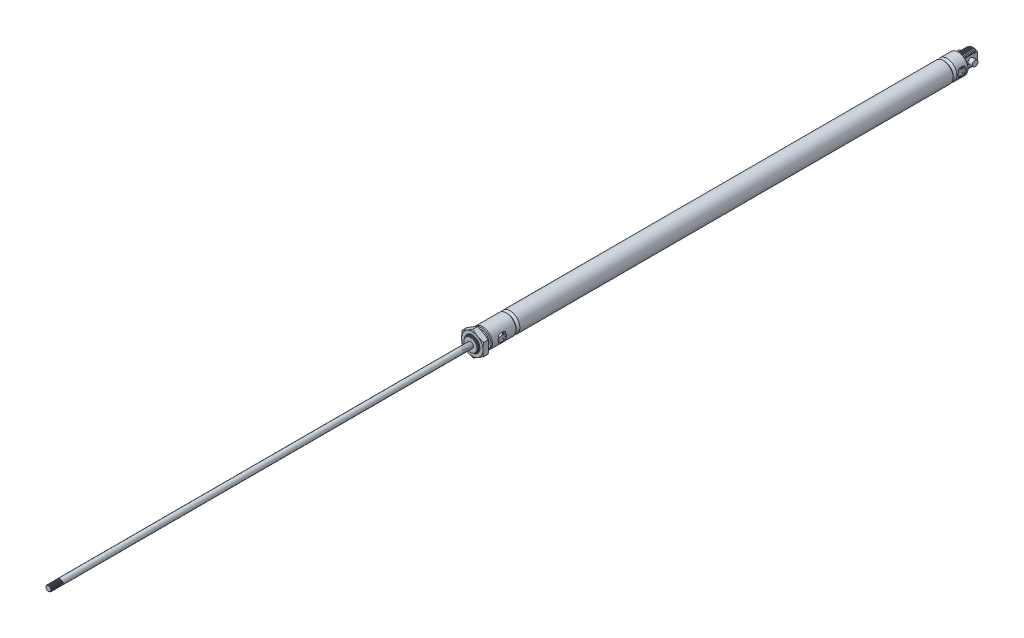
SolidWorks part; units mm, degrees
ref_plane "Front" through (0, 0, 0) normal (0, 0, 1) x (1, 0, 0)
ref_plane "Top" through (0, 0, 0) normal (0, 1, 0) x (1, 0, 0)
ref_plane "Right" through (0, 0, 0) normal (1, 0, 0) x (0, 0, -1)
sketch "Sketch1" plane through (0, 0, 0) normal (1, 0, 0) x (0, 0, -1)
  line L0 (-286.131, 0) -> (286.131, 0) construction
  line L1 (-273.431, -7.9375) -> (-273.431, 0) construction
  line L2 (-273.431, 7.9375) -> (-260.731, 7.9375) construction
  line L3 (-260.731, 0) -> (-260.731, 10.922)
  line L4 (-260.731, 10.922) -> (286.131, 10.922)
  line L5 (270.383, 10.922) -> (270.383, 7.9375) construction
  line L6 (270.383, 7.9375) -> (286.131, 7.9375) construction
  line L7 (286.131, 10.922) -> (286.131, 0)
  line L8 (286.131, 0) -> (301.879, 0) construction
  line L9 (-273.431, -7.9375) -> (-260.731, -7.9375) construction
  line L10 (-260.731, -7.9375) -> (-260.731, -10.922) construction
  line L11 (-260.731, -10.922) -> (286.131, -10.922) construction
  line L12 (270.383, -10.922) -> (270.383, -7.9375) construction
  line L13 (270.383, -7.9375) -> (286.131, -7.9375) construction
  line L14 (-263.017, 9.525) -> (-263.017, 0) construction
  line L18 (-273.431, 3.175) -> (-286.131, 3.175) construction
  line L19 (-286.131, 3.175) -> (-286.131, -3.175) construction
  line L20 (-286.131, -3.175) -> (-273.431, -3.175) construction
  line L24 (-273.431, 4.7625) -> (-263.017, 4.7625) construction
  line L25 (286.131, 0) -> (286.131, -10.922) construction
  line L26 (-273.431, 0) -> (-273.431, 7.9375) construction
  line L28 (-260.731, 0) -> (286.131, 0)
  line L29 (-268.224, 4.7625) -> (-268.224, 7.9375) construction
  line L30 (-260.731, 9.525) -> (-263.017, 9.525) construction
  dimension "D1" = 19.05
  dimension "J Flat" = 15.875
  dimension "E OD" = 21.844
  dimension "K Flat Depth" = 15.748
  dimension "RM Pilot" = 15.875
  dimension "G Pilot Length" = 12.7
  dimension "Shaft Dia" = 6.35
  dimension "A Thread Length" = 12.7
  dimension "Total Length" = 572.262
  dimension "V Pilot Length" = 2.286
revolve "Revolve1" add sketch "Sketch1" angle 360 about L8 reverse direction yes
sketch "Sketch58" plane through (0, 0, 0) normal (1, 0, 0) x (0, 0, -1)
  line L0 (286.131, 0) -> (301.879, 0) construction
  line L1 (270.383, 10.922) -> (286.131, 10.922)
  line L2 (270.383, 10.922) -> (270.383, 7.9375)
  line L3 (270.383, 7.9375) -> (286.131, 7.9375)
  line L4 (286.131, 10.922) -> (286.131, 7.9375)
  line L5 (286.131, 0) -> (301.879, 0) construction
revolve "Cut-Revolve25" cut sketch "Sketch58" angle 360 about L5
sketch "Sketch59" plane through (0, 0, -286.131) normal (0, 0, -1) x (-1, 0, 0)
  line L0 (-4.7625, -7.9375) -> (4.7625, 7.9375) construction
  line L1 (-4.7625, 7.9375) -> (4.7625, 7.9375)
  line L2 (-4.7625, 7.9375) -> (-4.7625, -7.9375)
  line L3 (-4.7625, -7.9375) -> (4.7625, -7.9375)
  line L4 (4.7625, 7.9375) -> (4.7625, -7.9375)
  dimension "D1" = 9.525
extrude "Cut-Extrude3" cut sketch "Sketch59" against normal up to surface (15.748 mm away) flip side to cut up to face at (7.9375, 0, -270.383)
chamfer "Chamfer1" distance 0.7874 angle 45 4 edges at (-10.922, 0, 260.731) (10.922, 0, -270.383) (0, 7.9375, -286.131) (0, -7.9375, -286.131)
sketch "Sketch4" plane through (0, 0, 0) normal (1, 0, 0) x (0, 0, -1)
  line L0 (-273.431, 0) -> (-273.431, 7.9375) construction
  line L1 (-286.131, 0) -> (286.131, 0) construction
  line L2 (-260.731, 0) -> (-260.731, 10.922) construction
  line L3 (-273.431, 7.9375) -> (-260.731, 7.9375) construction
  line L4 (-273.431, 0) -> (-273.431, 7.9375)
  line L5 (-273.431, 0) -> (-260.731, 0)
  line L6 (-260.731, 0) -> (-260.731, 7.9375)
  line L7 (-273.431, 7.9375) -> (-260.731, 7.9375)
  line L8 (-273.431, -7.9375) -> (-260.731, -7.9375) construction
  line L9 (-273.431, -7.9375) -> (-260.731, -7.9375) construction
revolve "Revolve2" add sketch "Sketch4" angle 360 about L5
sketch "Sketch5" plane through (0, 0, 0) normal (1, 0, 0) x (0, 0, -1)
  line L0 (-273.431, 7.9375) -> (-273.431, -7.9375) construction
  line L1 (-273.431, -7.9375) -> (-272.0199, -7.9375) construction
  line L2 (-272.0199, -7.9375) -> (-273.431, 7.9375) construction
  line L3 (-273.431, 7.9375) -> (-273.2553, 7.9531) construction
  line L4 (-273.2553, 7.9531) -> (-272.0254, 8.0624)
  line L5 (-272.0254, 8.0624) -> (-272.397, 7.2626)
  line L6 (-272.397, 7.2626) -> (-272.7484, 7.2314)
  line L7 (-272.7484, 7.2314) -> (-273.2553, 7.9531)
  line L8 (-272.6404, 8.0078) -> (-272.5727, 7.247) construction
  line L9 (-273.431, 7.9375) -> (-272.6341, 7.9375) construction
  line L10 (-272.6341, 7.9375) -> (-271.223, -7.9375) construction
  line L11 (-271.223, -7.9375) -> (-272.0199, -7.9375) construction
  line L12 (-273.431, 0) -> (-273.431, 7.9375) construction
  line L13 (-273.431, 7.9375) -> (-260.731, 7.9375) construction
  line L14 (-273.431, -7.9375) -> (-260.731, -7.9375) construction
  line L15 (-273.431, -0.1335) -> (-270.4261, 0.1335) construction
  point P19 (-271.9286, 0)
  dimension "D1" = 0.1764
  dimension "D2" = 0.3528
  dimension "Thread Pitch" = 1.4111
  dimension "D4" = 60
  dimension "D5" = 1.4111
revolve "Cut-Revolve2" cut sketch "Sketch5" angle 360 about L15
sketch "Sketch6" plane through (0, 0, 0) normal (1, 0, 0) x (0, 0, -1)
  line L0 (-273.431, 7.2314) -> (-272.208, 7.9375)
  line L1 (-272.208, 7.9375) -> (-273.431, 7.9375)
  line L2 (-273.431, 7.9375) -> (-273.431, 7.2314)
  line L3 (0, 0) -> (-273.431, 0) construction
  line L4 (-273.431, 0) -> (-273.431, 7.2314) construction
  line L5 (-273.431, 7.9375) -> (-260.731, 7.9375) construction
  line L6 (-273.431, 0) -> (-273.431, 7.9375) construction
  line L7 (-272.7484, 7.2314) -> (-273.431, 7.2314) construction
  dimension "D1" = 60
revolve "Cut-Revolve3" cut sketch "Sketch6" angle 360 about L3
pattern_linear "LPattern2" count 2 spacing 1.4111 along (0, 0, 1) count 9 spacing 1.4111 along (0, 0, -1) of "Cut-Revolve2"
sketch "Sketch53" plane through (0, 0, 0) normal (1, 0, 0) x (0, 0, -1)
  line L0 (-273.431, 0) -> (-260.731, 0) construction
  line L1 (-260.731, 7.9375) -> (-263.017, 7.9375)
  line L2 (-260.731, 7.9375) -> (-260.731, 0)
  line L3 (-260.731, 0) -> (-263.017, 0)
  line L4 (-263.017, 7.9375) -> (-263.017, 0)
  line L5 (-263.017, 9.525) -> (-263.017, 0) construction
  line L6 (-273.431, 7.9375) -> (-260.731, 7.9375) construction
  line L7 (-260.731, 0) -> (-260.731, 10.922) construction
revolve "Revolve4" add sketch "Sketch53" angle 360 about L3
sketch "Sketch62" plane through (0, 0, 0) normal (1, 0, 0) x (0, 0, -1)
  line L0 (270.383, 7.9375) -> (270.383, -7.9375) construction
  line L1 (270.383, -7.9375) -> (271.7941, -7.9375) construction
  line L2 (271.7941, -7.9375) -> (270.383, 7.9375) construction
  line L3 (270.383, 7.9375) -> (270.5587, 7.9531) construction
  line L4 (270.5587, 7.9531) -> (271.7886, 8.0624)
  line L5 (271.7886, 8.0624) -> (271.417, 7.2626)
  line L6 (271.417, 7.2626) -> (271.0656, 7.2314)
  line L7 (271.0656, 7.2314) -> (270.5587, 7.9531)
  line L8 (271.2413, 7.247) -> (271.1736, 8.0078) construction
  line L9 (270.383, 7.9375) -> (271.1799, 7.9375) construction
  line L10 (271.1799, 7.9375) -> (272.591, -7.9375) construction
  line L11 (272.591, -7.9375) -> (271.7941, -7.9375) construction
  line L12 (270.383, -0.1335) -> (273.3879, 0.1335) construction
  line L13 (270.383, 7.9375) -> (286.131, 7.9375) construction
  line L14 (270.383, 10.922) -> (270.383, 7.9375) construction
  line L15 (270.383, -7.9375) -> (286.131, -7.9375) construction
  point P13 (271.8854, 0)
  dimension "D1" = 60
  dimension "D2" = 0.3528
  dimension "D3" = 0.1764
  dimension "D4" = 1.4111
  dimension "D5" = 1.4111
revolve "Cut-Revolve26" cut sketch "Sketch62" angle 360 about L12
pattern_linear "LPattern5" count 11 spacing 1.4111 along (0, 0, -1) of "Cut-Revolve26"
sketch "Sketch60" plane through (0, 0, 0) normal (1, 0, 0) x (0, 0, -1)
  line L0 (-260.731, 0) -> (286.131, 0) construction
  line L1 (286.131, 10.922) -> (286.131, 0) construction
  circle A0 centre (279.019, 0) radius 3.175
  dimension "D2" = 6.35
  dimension "D1" = 7.112
extrude "Extrude2" add sketch "Sketch60" along normal mid plane 19.05
sketch "Sketch7" plane through (0, 0, 0) normal (1, 0, 0) x (0, 0, -1)
  line L0 (-273.431, 3.2004) -> (-257.556, 3.2004)
  line L1 (-257.556, 3.2004) -> (-257.556, 6.3627)
  line L2 (-257.556, 9.525) -> (-215.392, 9.525) construction
  line L3 (-209.042, 9.525) -> (248.158, 9.525)
  line L4 (248.158, 0) -> (-273.431, 0)
  line L5 (-273.431, 0) -> (-273.431, 3.2004)
  line L6 (-273.431, 0) -> (-273.431, 7.9375) construction
  line L7 (-260.731, 0) -> (286.131, 0) construction
  line L8 (248.158, 0) -> (301.879, 0) construction
  line L9 (-260.731, 0) -> (-260.731, 10.922) construction
  line L10 (248.158, 9.525) -> (248.158, 0)
  line L11 (253.111, 10.922) -> (254.508, 9.525)
  line L12 (-257.556, 6.3627) -> (-215.392, 6.3627)
  line L13 (-215.392, 6.3627) -> (-215.392, 9.525)
  line L14 (-257.556, 6.3627) -> (-257.556, 9.525) construction
  line L15 (-215.392, 9.525) -> (-209.042, 9.525)
  line L17 (254.508, 9.525) -> (254.508, 8.128)
  line L18 (254.508, 8.128) -> (257.302, 10.922)
  line L19 (257.302, 10.922) -> (253.111, 10.922)
  line L20 (254.508, 9.525) -> (254.508, 10.922) construction
  line L21 (-260.731, 10.922) -> (286.131, 10.922) construction
  line L22 (270.383, 10.922) -> (270.383, 7.9375) construction
  line L23 (-233.553, 10.922) -> (-232.156, 9.525)
  line L24 (-232.156, 9.525) -> (-232.156, 8.128)
  line L25 (-232.156, 8.128) -> (-229.362, 10.922)
  line L26 (-229.362, 10.922) -> (-233.553, 10.922)
  line L27 (-232.156, 9.525) -> (-232.156, 10.922) construction
  line L28 (-273.431, 3.175) -> (-286.131, 3.175) construction
  dimension "D1" = 0.0254
  dimension "Bore Dia" = 19.05
  dimension "D2" = 6.35
  dimension "D3" = 45
  dimension "Stroke" = 457.2
  dimension "D4" = 3.175
  dimension "D5" = 6.35
  dimension "D6" = 15.875
  dimension "D7" = 28.575
revolve "Cut-Revolve5" cut sketch "Sketch7" angle 360 about L8
sketch "Sketch8" plane through (0, 0, 0) normal (1, 0, 0) x (0, 0, -1)
  line L2 (241.808, 9.4742) -> (248.158, 9.4742)
  line L3 (248.158, 9.4742) -> (248.158, 0)
  line L4 (-286.131, 3.175) -> (-286.131, -3.175) construction
  line L6 (-286.131, 3.175) -> (-286.131, 0)
  line L7 (248.158, 0) -> (-286.131, 0)
  line L8 (-286.131, 0) -> (286.131, 0) construction
  line L9 (-209.042, 9.525) -> (248.158, 9.525) construction
  line L11 (248.158, 9.525) -> (248.158, 0) construction
  line L15 (241.808, 3.175) -> (241.808, 9.4742)
  line L16 (241.808, 3.175) -> (-286.131, 3.175)
  dimension "D1" = 0.0508
  dimension "D2" = 6.35
revolve "Revolve3" add sketch "Sketch8" angle 360 about L7
sketch "Sketch10" plane through (0, 0, 0) normal (1, 0, 0) x (0, 0, -1)
  line L0 (-286.131, 3.175) -> (-286.131, -3.175) construction
  line L1 (-286.131, -3.175) -> (-285.2239, -3.175) construction
  line L2 (-285.2239, -3.175) -> (-286.131, 3.175) construction
  line L3 (-286.131, 3.175) -> (-286.0187, 3.191) construction
  line L4 (-286.0187, 3.191) -> (-285.233, 3.3033)
  line L5 (-285.233, 3.3033) -> (-285.4442, 2.7771)
  line L6 (-285.4442, 2.7771) -> (-285.6687, 2.7451)
  line L7 (-285.6687, 2.7451) -> (-286.0187, 3.191)
  line L8 (-285.6259, 3.2472) -> (-285.5564, 2.7611) construction
  line L9 (-286.131, 3.175) -> (-285.6156, 3.175) construction
  line L10 (-285.6156, 3.175) -> (-284.7084, -3.175) construction
  line L11 (-284.7084, -3.175) -> (-285.2239, -3.175) construction
  line L12 (-286.131, 3.175) -> (-286.131, -3.175) construction
  line L13 (-273.431, 3.175) -> (-286.131, 3.175) construction
  line L14 (-286.131, -3.175) -> (-273.431, -3.175) construction
  line L15 (-286.131, -0.1384) -> (-284.193, 0.1384) construction
  point P19 (-285.162, 0)
  dimension "D1" = 0.1134
  dimension "D2" = 0.2268
  dimension "Shaft Thread Pitch" = 0.9071
  dimension "D4" = 0.9071
  dimension "D5" = 60
revolve "Cut-Revolve6" cut sketch "Sketch10" angle 360 about L15
sketch "Sketch11" plane through (0, 0, 0) normal (1, 0, 0) x (0, 0, -1)
  line L0 (-286.131, 3.175) -> (-285.3863, 3.175)
  line L1 (-285.3863, 3.175) -> (-286.131, 2.7451)
  line L2 (-286.131, 2.7451) -> (-286.131, 3.175)
  line L3 (0, 0) -> (-286.131, 0) construction
  line L4 (-286.131, 0) -> (-286.131, 2.7451) construction
  line L5 (-273.431, 3.175) -> (-286.131, 3.175) construction
  line L6 (-286.131, 3.175) -> (-286.131, -3.175) construction
  line L7 (-285.6687, 2.7451) -> (-286.131, 2.7451) construction
  dimension "D1" = 30
revolve "Cut-Revolve7" cut sketch "Sketch11" angle 360 about L3
pattern_linear "LPattern3" count 2 spacing 0.9071 along (0, 0, 1) count 14 spacing 0.9071 along (0, 0, -1) of "Cut-Revolve6"
pattern_linear "LPattern4" count 2 spacing 457.2 along (0, 0, 1) of bodies 122
ref_plane "Plane4" through (0, 0, -263.271) normal (0, 0, -1) x (-1, 0, 0)
ref_axis "Axis3" through (0, -15.123, -263.271) along (0, 1, 0)
ref_plane "Plane6" through (0, 0, -263.271) normal (0, 0, 1) x (1, 0, 0)
sketch "Sketch13" plane through (-356.4319, -1.7517, -263.271) normal (0, 0, 1) x (1, 0, 0)
  line L0 (355.9239, 1.7517) -> (355.9239, 5.9543)
  line L1 (355.9239, 5.9543) -> (356.3686, 6.7833) construction
  line L2 (356.3686, 6.7833) -> (356.8642, 5.9837) construction
  line L3 (356.8642, 5.9837) -> (357.3089, 6.8127) construction
  line L4 (357.3089, 6.8127) -> (357.8045, 6.013) construction
  line L5 (356.8811, 6.0153) -> (357.2919, 6.781)
  line L6 (357.2919, 6.781) -> (357.3278, 6.7822)
  line L7 (357.3278, 6.7822) -> (357.7856, 6.0435)
  line L8 (357.7856, 6.0435) -> (357.8214, 6.0446)
  line L9 (355.9239, 5.9543) -> (357.8045, 6.013) construction
  line L10 (356.3686, 6.7833) -> (357.3089, 6.8127) construction
  line L11 (356.1462, 6.3688) -> (357.5567, 6.4128) construction
  line L12 (355.9239, 1.7517) -> (351.7213, 1.7517) construction
  line L13 (357.8214, 6.0446) -> (358.2322, 6.8104)
  line L14 (355.9409, 5.9859) -> (356.3516, 6.7517)
  line L15 (356.3516, 6.7517) -> (356.3875, 6.7528)
  line L16 (356.3875, 6.7528) -> (356.8453, 6.0141)
  line L17 (356.8453, 6.0141) -> (356.8811, 6.0153)
  line L18 (356.1462, 6.3688) -> (355.9239, 6.3618) construction
  line L19 (355.9239, 6.3618) -> (355.9239, 5.9543) construction
  line L20 (356.1462, -2.8653) -> (355.9239, -2.8584) construction
  line L21 (355.9409, 5.9859) -> (355.9239, 5.9543)
  line L22 (358.2322, 6.8104) -> (358.268, 6.8116)
  line L23 (358.268, 6.8116) -> (358.7258, 6.0729)
  line L24 (358.7258, 6.0729) -> (358.7617, 6.074)
  line L25 (358.7617, 6.074) -> (359.1725, 6.8398)
  line L26 (359.1725, 6.8398) -> (359.2083, 6.8409)
  line L27 (359.2083, 6.8409) -> (359.6661, 6.1023)
  line L28 (359.6661, 6.1023) -> (359.702, 6.1034)
  line L29 (359.702, 6.1034) -> (360.1128, 6.8692)
  line L30 (360.1128, 6.8692) -> (360.1486, 6.8703)
  line L31 (360.1486, 6.8703) -> (360.6064, 6.1317)
  line L32 (360.6064, 6.1317) -> (360.6423, 6.1328)
  line L33 (360.6423, 6.1328) -> (361.053, 6.8986)
  line L34 (361.053, 6.8986) -> (361.0889, 6.8997)
  line L35 (361.0889, 6.8997) -> (361.5467, 6.1611)
  line L36 (361.5467, 6.1611) -> (361.5825, 6.1622)
  line L37 (361.5825, 6.1622) -> (361.9933, 6.928)
  line L38 (361.9933, 6.928) -> (362.0292, 6.9291)
  line L39 (362.0292, 6.9291) -> (362.487, 6.1904)
  line L40 (362.487, 6.1904) -> (362.5228, 6.1916)
  line L41 (362.5228, 6.1916) -> (362.9336, 6.9574)
  line L42 (362.9336, 6.9574) -> (362.9695, 6.9585)
  line L43 (362.9695, 6.9585) -> (363.4273, 6.2198)
  line L44 (363.4273, 6.2198) -> (363.4631, 6.221)
  line L45 (363.4631, 6.221) -> (363.8739, 6.9867)
  line L46 (363.8739, 6.9867) -> (363.9097, 6.9879)
  line L47 (363.9097, 6.9879) -> (364.3675, 6.2492)
  line L48 (364.3675, 6.2492) -> (364.4034, 6.2503)
  line L49 (364.4034, 6.2503) -> (364.8142, 7.0161)
  line L50 (364.8142, 7.0161) -> (364.85, 7.0173)
  line L51 (364.85, 7.0173) -> (365.3078, 6.2786)
  line L52 (365.3078, 6.2786) -> (365.3437, 6.2797)
  line L53 (365.3437, 6.2797) -> (365.7545, 7.0455)
  line L54 (365.7545, 7.0455) -> (365.7903, 7.0466)
  line L55 (365.7903, 7.0466) -> (366.2481, 6.308)
  line L56 (366.2481, 6.308) -> (366.284, 6.3091)
  line L57 (366.284, 6.3091) -> (366.6947, 7.0749)
  line L58 (366.6947, 7.0749) -> (366.7306, 7.076)
  line L59 (366.7306, 7.076) -> (367.1884, 6.3374)
  line L60 (367.1884, 6.3374) -> (367.2242, 6.3385)
  line L61 (367.2242, 6.3385) -> (367.635, 7.1043)
  line L62 (367.635, 7.1043) -> (367.6709, 7.1054)
  line L63 (367.6709, 7.1054) -> (368.1287, 6.3668)
  line L64 (368.1287, 6.3668) -> (368.1645, 6.3679)
  line L65 (368.1645, 6.3679) -> (368.5753, 7.1337)
  line L66 (368.5753, 7.1337) -> (368.6111, 7.1348)
  line L67 (368.6111, 7.1348) -> (369.0689, 6.3961)
  line L68 (369.0689, 6.3961) -> (369.1048, 6.3973)
  line L69 (369.1048, 6.3973) -> (369.5156, 7.1631)
  line L70 (369.5156, 7.1631) -> (369.5514, 7.1642)
  line L71 (369.5514, 7.1642) -> (370.0092, 6.4255)
  line L72 (370.0092, 6.4255) -> (370.0451, 6.4267)
  line L73 (355.9239, 1.7517) -> (370.0451, 1.7517)
  line L74 (370.0451, 1.7517) -> (370.0451, 6.4267)
  line L75 (356.3696, 6.7522) -> (356.3686, 6.7833) construction
  line L80 (356.4319, 1.7517) -> (367.3539, 1.7517) construction
  circle A0 centre (356.4319, 1.7517) radius 10.922 construction
  circle A1 centre (356.4319, 1.7517) radius 10.922 construction
  dimension "D1" = 60
  dimension "D2" = 0.031
  dimension "E0" = 9.2202
  dimension "D3" = 0.0359
  dimension "Thread Pitch" = 0.9407
  dimension "Thread Taper" = 3.58
  dimension "L4 Thread Length" = 11.43
revolve "Cut-Revolve22" cut sketch "Sketch13" angle 360 about L12
ref_plane "Plane7" through (0, 0, 248.793) normal (0, 0, 1) x (1, 0, 0)
sketch "Sketch64" plane through (-356.4319, -1.7517, 248.793) normal (0, 0, 1) x (1, 0, 0)
  line L0 (355.9239, 1.7517) -> (355.9239, 5.9543)
  line L1 (355.9239, 5.9543) -> (356.3686, 6.7833) construction
  line L2 (356.3686, 6.7833) -> (356.8642, 5.9837) construction
  line L3 (356.8642, 5.9837) -> (357.3089, 6.8127) construction
  line L4 (357.3089, 6.8127) -> (357.8045, 6.013) construction
  line L5 (356.8896, 6.0311) -> (357.2834, 6.7652)
  line L6 (357.2834, 6.7652) -> (357.3372, 6.7669)
  line L7 (357.3372, 6.7669) -> (357.7761, 6.0588)
  line L8 (357.7761, 6.0588) -> (357.8299, 6.0604)
  line L9 (355.9239, 5.9543) -> (357.8045, 6.013) construction
  line L10 (356.3686, 6.7833) -> (357.3089, 6.8127) construction
  line L11 (356.1462, 6.3688) -> (357.5567, 6.4128) construction
  line L12 (355.9239, 1.7517) -> (351.7213, 1.7517) construction
  line L13 (357.8299, 6.0604) -> (358.2237, 6.7946)
  line L14 (355.9493, 6.0017) -> (356.3432, 6.7359)
  line L15 (356.3432, 6.7359) -> (356.3969, 6.7375)
  line L16 (356.3969, 6.7375) -> (356.8358, 6.0294)
  line L17 (356.8358, 6.0294) -> (356.8896, 6.0311)
  line L18 (356.1462, 6.3688) -> (355.9239, 6.3618) construction
  line L19 (355.9239, 6.3618) -> (355.9239, 5.9543) construction
  line L20 (356.1462, -2.8653) -> (355.9239, -2.8584) construction
  line L21 (355.9493, 6.0017) -> (355.9239, 5.9543)
  line L22 (358.2237, 6.7946) -> (358.2775, 6.7963)
  line L23 (358.2775, 6.7963) -> (358.7164, 6.0882)
  line L24 (358.7164, 6.0882) -> (358.7702, 6.0898)
  line L25 (358.7702, 6.0898) -> (359.164, 6.824)
  line L26 (359.164, 6.824) -> (359.2178, 6.8257)
  line L27 (359.2178, 6.8257) -> (359.6567, 6.1175)
  line L28 (359.6567, 6.1175) -> (359.7105, 6.1192)
  line L29 (359.7105, 6.1192) -> (360.1043, 6.8534)
  line L30 (360.1043, 6.8534) -> (360.1581, 6.8551)
  line L31 (360.1581, 6.8551) -> (360.597, 6.1469)
  line L32 (360.597, 6.1469) -> (360.6507, 6.1486)
  line L33 (360.6507, 6.1486) -> (361.0446, 6.8828)
  line L34 (361.0446, 6.8828) -> (361.0983, 6.8845)
  line L35 (361.0983, 6.8845) -> (361.5372, 6.1763)
  line L36 (361.5372, 6.1763) -> (361.591, 6.178)
  line L37 (361.591, 6.178) -> (361.9849, 6.9122)
  line L38 (361.9849, 6.9122) -> (362.0386, 6.9139)
  line L39 (362.0386, 6.9139) -> (362.4775, 6.2057)
  line L40 (362.4775, 6.2057) -> (362.5313, 6.2074)
  line L41 (362.5313, 6.2074) -> (362.9251, 6.9416)
  line L42 (362.9251, 6.9416) -> (362.9789, 6.9432)
  line L43 (362.9789, 6.9432) -> (363.4178, 6.2351)
  line L44 (363.4178, 6.2351) -> (363.4716, 6.2368)
  line L45 (363.4716, 6.2368) -> (363.8654, 6.9709)
  line L46 (363.8654, 6.9709) -> (363.9192, 6.9726)
  line L47 (363.9192, 6.9726) -> (364.3581, 6.2645)
  line L48 (364.3581, 6.2645) -> (364.4119, 6.2661)
  line L49 (364.4119, 6.2661) -> (364.8057, 7.0003)
  line L50 (364.8057, 7.0003) -> (364.8595, 7.002)
  line L51 (364.8595, 7.002) -> (365.2984, 6.2938)
  line L52 (365.2984, 6.2938) -> (365.3521, 6.2955)
  line L53 (365.3521, 6.2955) -> (365.746, 7.0297)
  line L54 (365.746, 7.0297) -> (365.7997, 7.0314)
  line L55 (365.7997, 7.0314) -> (366.2387, 6.3232)
  line L56 (366.2387, 6.3232) -> (366.2924, 6.3249)
  line L57 (366.2924, 6.3249) -> (366.6863, 7.0591)
  line L58 (366.6863, 7.0591) -> (366.74, 7.0608)
  line L59 (366.74, 7.0608) -> (367.1789, 6.3526)
  line L60 (367.1789, 6.3526) -> (367.2327, 6.3543)
  line L61 (367.2327, 6.3543) -> (367.6265, 7.0885)
  line L62 (367.6265, 7.0885) -> (367.6803, 7.0902)
  line L63 (367.6803, 7.0902) -> (368.1192, 6.382)
  line L64 (368.1192, 6.382) -> (368.173, 6.3837)
  line L65 (368.173, 6.3837) -> (368.5668, 7.1179)
  line L66 (368.5668, 7.1179) -> (368.6206, 7.1196)
  line L67 (368.6206, 7.1196) -> (369.0595, 6.4114)
  line L68 (369.0595, 6.4114) -> (369.1133, 6.4131)
  line L69 (369.1133, 6.4131) -> (369.5071, 7.1473)
  line L70 (369.5071, 7.1473) -> (369.5609, 7.1489)
  line L71 (369.5609, 7.1489) -> (369.9998, 6.4408)
  line L72 (369.9998, 6.4408) -> (370.0536, 6.4425)
  line L73 (355.9239, 1.7517) -> (370.0536, 1.7517)
  line L74 (370.0536, 1.7517) -> (370.0536, 6.4425)
  line L75 (356.37, 6.7367) -> (356.3686, 6.7833) construction
  line L80 (356.4319, 1.7517) -> (367.3539, 1.7517) construction
  circle A1 centre (356.4319, 1.7517) radius 10.922 construction
  circle A2 centre (356.4319, 1.7517) radius 10.922 construction
  dimension "D1" = 60
  dimension "D2" = 0.0466
  dimension "D3" = 0.0538
  dimension "Thread Pitch" = 0.9407
  dimension "D4" = 9.2202
  dimension "Thread Taper" = 3.58
  dimension "L4 Thread Length" = 11.43
revolve "Cut-Revolve27" cut sketch "Sketch64" angle 360 about L73
ref_plane "Plane2" through (0, 0, 268.224) normal (0, 0, 1) x (1, 0, 0)
sketch "Sketch54" plane through (0, 0, 268.224) normal (0, 0, 1) x (1, 0, 0)
  line L1 (0, 13.7482) -> (-11.9062, 6.8741)
  line L2 (-11.9062, 6.8741) -> (-11.9062, -6.8741)
  line L3 (-11.9062, -6.8741) -> (0, -13.7482)
  line L4 (0, -13.7482) -> (11.9062, -6.8741)
  line L5 (11.9062, -6.8741) -> (11.9062, 6.8741)
  line L6 (11.9062, 6.8741) -> (0, 13.7482)
  circle A0 centre (0, 0) radius 11.9062 construction
  circle A1 centre (0, 0) radius 7.9375
  dimension "Nut Hex" = 23.8125
extrude "Extrude1" add sketch "Sketch54" along normal mid plane 6.35 separate body
sketch "Sketch55" plane through (0, 0, 0) normal (1, 0, 0) x (0, 0, -1)
  line L0 (-270.7286, 13.7482) -> (-271.399, 13.7482)
  line L1 (-271.399, 13.7482) -> (-271.399, 11.9062)
  line L2 (-271.399, 11.9062) -> (-270.7286, 13.7482)
  line L3 (-265.7194, 13.7482) -> (-265.049, 13.7482)
  line L4 (-265.049, 13.7482) -> (-265.049, 11.9062)
  line L5 (-265.049, 11.9062) -> (-265.7194, 13.7482)
  line L6 (-271.399, 11.9062) -> (-265.049, 11.9062) construction
  line L7 (-271.399, 13.7482) -> (-265.049, 13.7482) construction
  line L10 (0, 0) -> (-271.399, 0) construction
  line L11 (-271.399, 0) -> (-271.399, 11.9062) construction
  line L12 (-271.399, 8.6079) -> (-271.399, 7.9375)
  line L13 (-271.399, 7.9375) -> (-270.7286, 7.9375)
  line L14 (-270.7286, 7.9375) -> (-271.399, 8.6079)
  line L15 (-265.049, 8.6079) -> (-265.049, 7.9375)
  line L16 (-265.049, 7.9375) -> (-265.7194, 7.9375)
  line L17 (-265.7194, 7.9375) -> (-265.049, 8.6079)
  line L19 (-270.7286, 13.7482) -> (-270.7286, 7.9375) construction
  line L20 (-265.049, 6.8741) -> (-265.049, 13.7482) construction
  line L21 (-271.399, 6.8741) -> (-271.399, 13.7482) construction
  line L22 (-265.049, 7.9375) -> (-271.399, 7.9375) construction
  dimension "D1" = 20
  dimension "D2" = 23.8125
  dimension "D3" = 45
revolve "Cut-Revolve24" cut sketch "Sketch55" angle 360 about L10
equation "\"D1@Chamfer1\"=\"K Flat Depth@Sketch1\"/20"
equation "\"D1@Sketch5\"=\"Thread Pitch@Sketch5\"/8"
equation "\"D2@Sketch5\"=\"Thread Pitch@Sketch5\"/4"
equation "\"D5@Sketch5\"=\"Thread Pitch@Sketch5\""
equation "\"D3@LPattern2\"=\"Thread Pitch@Sketch5\""
equation "\"D4@LPattern2\"=\"Thread Pitch@Sketch5\""
equation "\"D2@LPattern2\"=\"G Pilot Length@Sketch1\"/\"Thread Pitch@Sketch5\""
equation "\"D1@Sketch10\"=\"Shaft Thread Pitch@Sketch10\"/8"
equation "\"D2@Sketch10\"=\"Shaft Thread Pitch@Sketch10\"/4"
equation "\"D4@Sketch10\"=\"Shaft Thread Pitch@Sketch10\""
equation "\"D3@LPattern3\"=\"Shaft Thread Pitch@Sketch10\""
equation "\"D4@LPattern3\"=\"Shaft Thread Pitch@Sketch10\""
equation "\"D2@LPattern3\"=\"A Thread Length@Sketch1\"/\"Shaft Thread Pitch@Sketch10\""
equation "\"D3@LPattern4\"=\"Stroke@Sketch7\""
equation "\"D2@Sketch13\"=\"Thread Pitch@Sketch13\"*.033"
equation "\"D2@Sketch55\"=\"Nut Hex@Sketch54\""
equation "\"D3@Sketch62\"=\"D4@Sketch62\"/8"
equation "\"D2@Sketch62\"=\"D4@Sketch62\"/4"
equation "\"D5@Sketch62\"=\"D4@Sketch62\""
equation "\"D4@Sketch62\"=\"Thread Pitch@Sketch5\""
equation "\"D3@LPattern5\"=\"Thread Pitch@Sketch5\""
equation "\"D1@LPattern5\"=\"K Flat Depth@Sketch1\"/\"Thread Pitch@Sketch5\""
